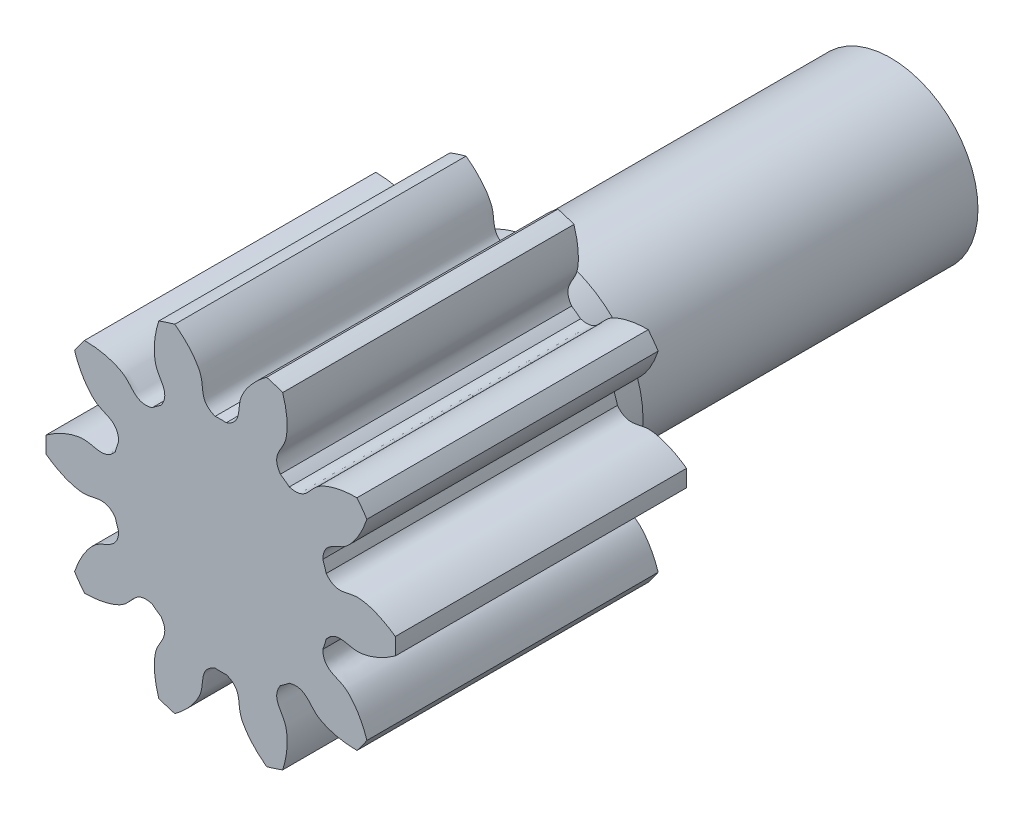
SolidWorks part; units mm, degrees
ref_plane "前视基准面" through (0, 0, 0) normal (0, 0, 1) x (1, 0, 0)
ref_plane "上视基准面" through (0, 0, 0) normal (0, 1, 0) x (1, 0, 0)
ref_plane "右视基准面" through (0, 0, 0) normal (1, 0, 0) x (0, 0, -1)
other "Configuration Table"
sketch "草图1" plane through (0, 0, 0) normal (0, 0, 1) x (1, 0, 0)
  circle A0 centre (0, 0) radius 6
extrude "凸台-拉伸1" add sketch "草图1" along normal blind 10
ref_axis "基准轴1" through (0, 0, -0.5) along (0, 0, 1)
sketch "草图2" plane through (0, 0, 0) normal (0, 0, 1) x (1, 0, 0)
  line L0 (0, 0) -> (0, 6) construction
  circle A0 centre (0, 0) radius 6 construction
  arc A1 (0.1905, 3.7452) -> (-0.1905, 3.7452) centre (0, 0) ccw
  arc A2 (4.2536, 6.6943) -> (-4.2536, 6.6943) centre (0, 0) ccw
  spline S0 degree 3 poles (0.1905, 3.7452) (0.7254, 3.9406) (0.5738, 4.3706) (0.6887, 4.7247) (0.6945, 4.7415) (0.7013, 4.7601) (0.7092, 4.7802) (0.7182, 4.8019) (0.7284, 4.8251) (0.7398, 4.8499) (0.7526, 4.8761) (0.7667, 4.9037) (0.7823, 4.9326) (0.7994, 4.9629) (0.818, 4.9945) (0.8382, 5.0273) (0.8601, 5.0612) (0.8838, 5.0963) (0.9092, 5.1324) (0.9364, 5.1695) (0.9655, 5.2076) (0.9966, 5.2466) (1.0296, 5.2863) (1.0646, 5.3268) (1.1017, 5.368) (1.1409, 5.4099) (1.1823, 5.4522) (1.2258, 5.4951) (1.2715, 5.5384) (1.3195, 5.582) (1.3698, 5.6259) (1.4223, 5.67) (1.4772, 5.7142) (1.5345, 5.7584) (1.5941, 5.8026) (1.6562, 5.8467) (1.7206, 5.8906) (1.7876, 5.9343) (1.8569, 5.9775) (1.9287, 6.0204) (2.0031, 6.0627) (2.0798, 6.1044) (2.1591, 6.1455) (2.2409, 6.1858) (2.3251, 6.2252) (2.4119, 6.2638) (2.5011, 6.3013) (2.5928, 6.3377) (2.687, 6.3729) (2.7836, 6.4069) (2.8827, 6.4395) (2.9842, 6.4706) (3.0882, 6.5003) (3.1945, 6.5283) (3.3032, 6.5547) (3.4142, 6.5792) (3.5275, 6.602) (3.6431, 6.6228) (3.761, 6.6415) (3.8811, 6.6582) (4.0453, 6.6776) (4.1698, 6.6886) (4.2536, 6.6943) knots 0 0 0 0 0.201721 0.204697 0.208023 0.211699 0.215726 0.220102 0.224829 0.229906 0.235332 0.241109 0.247237 0.253714 0.260541 0.267719 0.275246 0.283124 0.291352 0.29993 0.308858 0.318136 0.327765 0.337743 0.348072 0.358751 0.36978 0.381158 0.392888 0.404967 0.417396 0.430176 0.443305 0.456785 0.470615 0.484795 0.499325 0.514205 0.529435 0.545016 0.560946 0.577227 0.593858 0.610839 0.62817 0.645851 0.663882 0.682264 0.700995 0.720077 0.739509 0.759291 0.779423 0.799905 0.820737 0.84192 0.863452 0.885335 0.907568 0.930151 0.953084 1 1 1 1
  spline S1 degree 3 poles (-0.1905, 3.7452) (-0.7254, 3.9406) (-0.5738, 4.3706) (-0.6887, 4.7247) (-0.6945, 4.7415) (-0.7013, 4.7601) (-0.7092, 4.7802) (-0.7182, 4.8019) (-0.7284, 4.8251) (-0.7398, 4.8499) (-0.7526, 4.8761) (-0.7667, 4.9037) (-0.7823, 4.9326) (-0.7994, 4.9629) (-0.818, 4.9945) (-0.8382, 5.0273) (-0.8601, 5.0612) (-0.8838, 5.0963) (-0.9092, 5.1324) (-0.9364, 5.1695) (-0.9655, 5.2076) (-0.9966, 5.2466) (-1.0296, 5.2863) (-1.0646, 5.3268) (-1.1017, 5.368) (-1.1409, 5.4099) (-1.1823, 5.4522) (-1.2258, 5.4951) (-1.2715, 5.5384) (-1.3195, 5.582) (-1.3698, 5.6259) (-1.4223, 5.67) (-1.4772, 5.7142) (-1.5345, 5.7584) (-1.5941, 5.8026) (-1.6562, 5.8467) (-1.7206, 5.8906) (-1.7876, 5.9343) (-1.8569, 5.9775) (-1.9287, 6.0204) (-2.0031, 6.0627) (-2.0798, 6.1044) (-2.1591, 6.1455) (-2.2409, 6.1858) (-2.3251, 6.2252) (-2.4119, 6.2638) (-2.5011, 6.3013) (-2.5928, 6.3377) (-2.687, 6.3729) (-2.7836, 6.4069) (-2.8827, 6.4395) (-2.9842, 6.4706) (-3.0882, 6.5003) (-3.1945, 6.5283) (-3.3032, 6.5547) (-3.4142, 6.5792) (-3.5275, 6.602) (-3.6431, 6.6228) (-3.761, 6.6415) (-3.8811, 6.6582) (-4.0453, 6.6776) (-4.1698, 6.6886) (-4.2536, 6.6943) knots 0 0 0 0 0.201721 0.204697 0.208023 0.211699 0.215726 0.220102 0.224829 0.229906 0.235332 0.241109 0.247237 0.253714 0.260541 0.267719 0.275246 0.283124 0.291352 0.29993 0.308858 0.318136 0.327765 0.337743 0.348072 0.358751 0.36978 0.381158 0.392888 0.404967 0.417396 0.430176 0.443305 0.456785 0.470615 0.484795 0.499325 0.514205 0.529435 0.545016 0.560946 0.577227 0.593858 0.610839 0.62817 0.645851 0.663882 0.682264 0.700995 0.720077 0.739509 0.759291 0.779423 0.799905 0.820737 0.84192 0.863452 0.885335 0.907568 0.930151 0.953084 1 1 1 1
extrude "切除-拉伸1" cut sketch "草图2" along normal through all
pattern_circular "阵列(圆周)1" count 10 every 36 about axis through (0, 0, -0.5) along (0, 0, 1) of "切除-拉伸1"
sketch "草图3" plane through (0, 0, 0) normal (0, 0, 1) x (1, 0, 0)
  circle A0 centre (0, 0) radius 5 construction
  dimension "Dn" = 10
sketch "草图4" plane through (0, 0, 0) normal (0, 0, -1) x (-1, 0, 0)
  circle A0 centre (0, 0) radius 3
  dimension "D1" = 6
extrude "凸台-拉伸2" add sketch "草图4" along normal blind 13
sketch "草图5" plane through (0, 0, 0) normal (0, 0, -1) x (-1, 0, 0)
  circle A0 centre (0, 0) radius 3.5
  dimension "D1" = 7
extrude "凸台-拉伸3" add sketch "草图5" along normal blind 1
